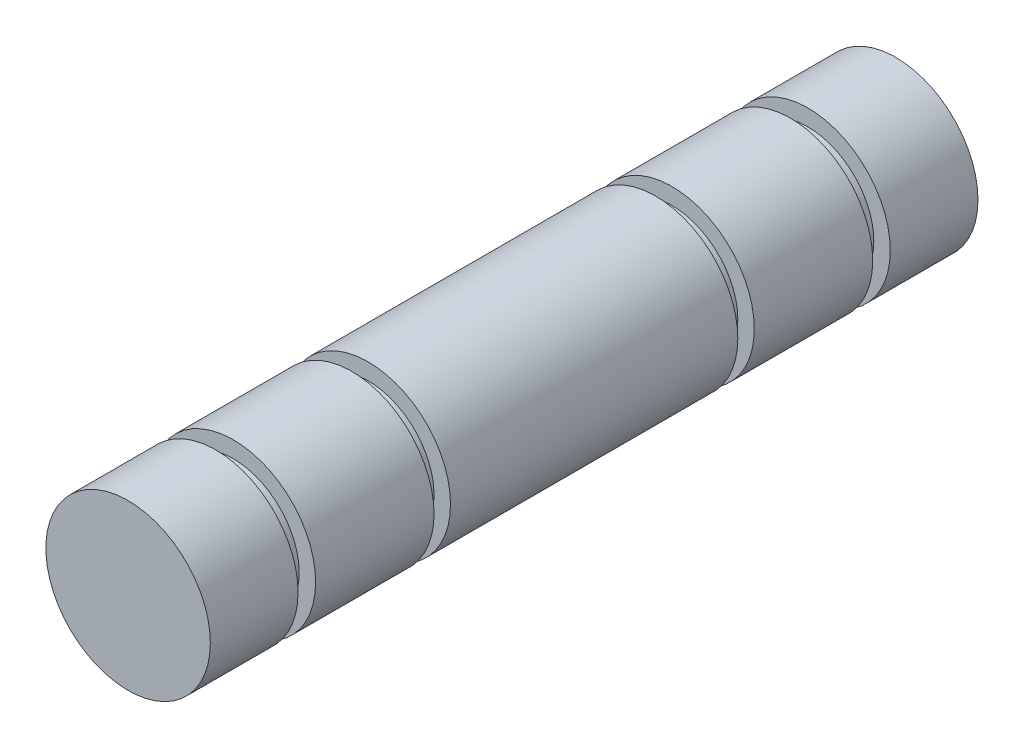
SolidWorks part; units mm, degrees
ref_plane "Front Plane" through (0, 0, 0) normal (0, 0, 1) x (1, 0, 0)
ref_plane "Top Plane" through (0, 0, 0) normal (0, 1, 0) x (1, 0, 0)
ref_plane "Right Plane" through (0, 0, 0) normal (1, 0, 0) x (0, 0, -1)
sketch "Sketch1" plane through (0, 0, 0) normal (0, 0, 1) x (1, 0, 0)
  circle A0 centre (0, 0) radius 4.7625
  dimension "D1" = 9.525
extrude "Boss-Extrude1" add sketch "Sketch1" along normal mid plane 44.45
sketch "Sketch2" plane through (0, 0, 0) normal (0, 1, 0) x (1, 0, 0)
  line L0 (4.7625, -22.225) -> (4.7625, 22.225) construction
  line L1 (4.7625, 17.145) -> (3.81, 17.145)
  line L2 (4.7625, 17.145) -> (4.7625, 16.129)
  line L3 (4.7625, 16.129) -> (3.81, 16.129)
  line L4 (3.81, 17.145) -> (3.81, 16.129)
  line L5 (4.7625, 22.225) -> (-4.7625, 22.225) construction
  line L6 (4.7625, -16.129) -> (3.81, -16.129)
  line L7 (4.7625, -16.129) -> (4.7625, -17.145)
  line L8 (4.7625, -17.145) -> (3.81, -17.145)
  line L9 (3.81, -16.129) -> (3.81, -17.145)
  line L10 (-4.7625, -22.225) -> (4.7625, -22.225) construction
  line L11 (4.7625, -22.225) -> (4.7625, 22.225) construction
  line L12 (4.7625, 9.271) -> (3.81, 9.271)
  line L13 (4.7625, 9.271) -> (4.7625, 8.3185)
  line L14 (4.7625, 8.3185) -> (3.81, 8.3185)
  line L15 (3.81, 9.271) -> (3.81, 8.3185)
  line L17 (4.7625, -8.3185) -> (3.81, -8.3185)
  line L18 (4.7625, -8.3185) -> (4.7625, -9.271)
  line L19 (4.7625, -9.271) -> (3.81, -9.271)
  line L20 (3.81, -8.3185) -> (3.81, -9.271)
  point P10 (3.81, 16.637)
  dimension "D1" = 0.9525
  dimension "D2" = 0.9525
  dimension "D3" = 1.016
  dimension "D4" = 1.016
  dimension "D5" = 5.08
  dimension "D6" = 5.08
  dimension "D7" = 0.9525
  dimension "D8" = 0.9525
  dimension "D9" = 6.858
  dimension "D10" = 0.9525
  dimension "D11" = 0.9525
  dimension "D12" = 6.858
ref_axis "Axis1" through (0, 0, 22.225) along (0, 0, -1)
revolve "Cut-Revolve1" cut sketch "Sketch2" angle 360 about axis through (0, 0, 22.225) along (0, 0, -1)
